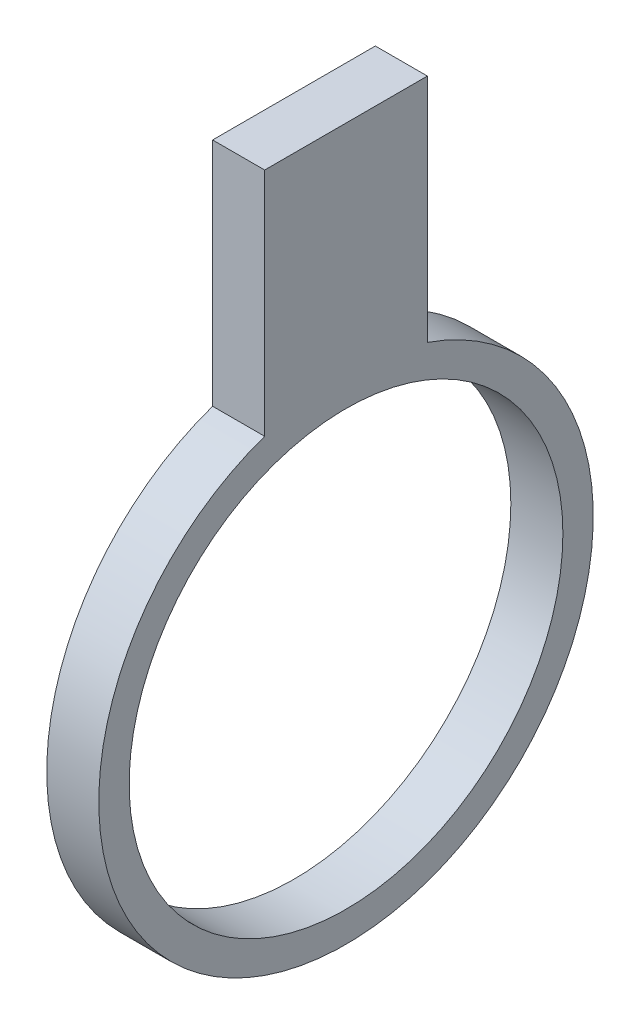
SolidWorks part; units mm, degrees
ref_plane "Front Plane" through (0, 0, 0) normal (0, 0, 1) x (1, 0, 0)
ref_plane "Top Plane" through (0, 0, 0) normal (0, 1, 0) x (1, 0, 0)
ref_plane "Right Plane" through (0, 0, 0) normal (1, 0, 0) x (0, 0, -1)
sketch "Sketch1" plane through (0, 0, 0) normal (1, 0, 0) x (0, 0, -1)
  circle A1 centre (0, 0) radius 28.5
  dimension "D2" = 57
extrude "Boss-Extrude1" add sketch "Sketch1" along normal mid plane 6
sketch "Sketch2" plane through (3, 0, 0) normal (1, 0, 0) x (0, 0, -1)
  circle A0 centre (0, 0) radius 25
  dimension "D1" = 50
extrude "Cut-Extrude1" cut sketch "Sketch2" against normal through all
sketch "Sketch3" plane through (0, 0, 0) normal (1, 0, 0) x (0, 0, -1)
  line L0 (-9.3792, 53.5) -> (-9.3792, 26.9125)
  line L1 (-9.3792, 53.5) -> (9.3792, 53.5)
  line L5 (9.3792, 53.5) -> (9.3792, 26.9125)
  circle A3 centre (0, 0) radius 28.5 construction
  arc A4 (9.3792, 26.9125) -> (-9.3792, 26.9125) centre (0, 0) ccw
  point P0 (0, 30.4396)
  dimension "D1" = 25
extrude "Boss-Extrude2" add sketch "Sketch3" along normal mid plane 6
